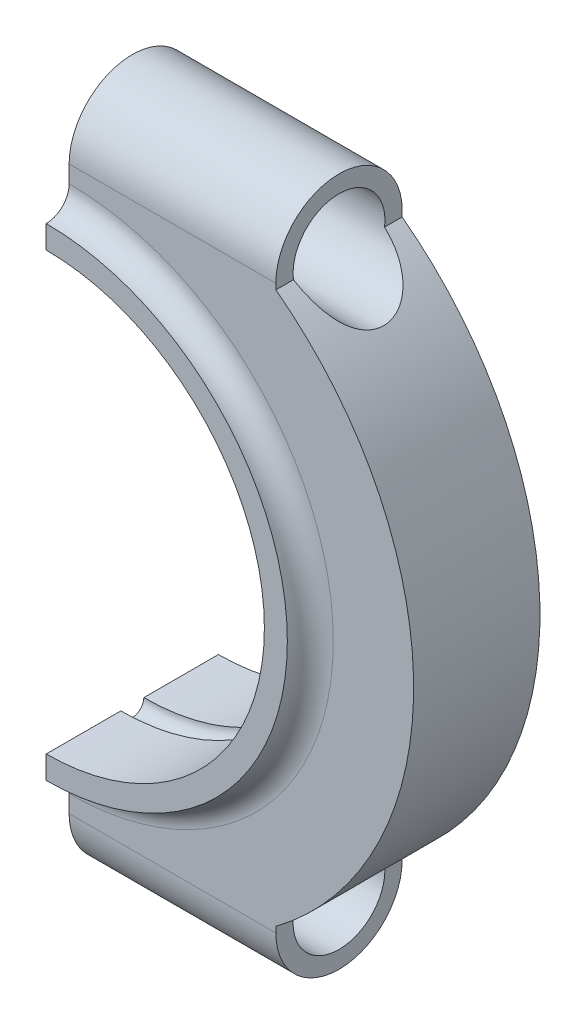
SolidWorks part; units mm, degrees
ref_plane "Front Plane" through (0, 0, 0) normal (0, 0, 1) x (1, 0, 0)
ref_plane "Top Plane" through (0, 0, 0) normal (0, 1, 0) x (1, 0, 0)
ref_plane "Right Plane" through (0, 0, 0) normal (1, 0, 0) x (0, 0, -1)
sketch "Sketch1" plane through (0, 0, 0) normal (0, 0, 1) x (1, 0, 0)
  line L0 (3937, 0) -> (0, 0) construction
  line L1 (-0.057, 762) -> (457.905, 762)
  line L2 (757.2512, 439.1989) -> (773.4704, 438.2517)
  line L3 (1676.1325, 385.5364) -> (3300.7334, 290.6599)
  line L4 (1676.1325, -385.5364) -> (3300.7334, -290.6599)
  line L5 (-0.057, -762) -> (457.905, -762)
  line L6 (-0.057, 762) -> (0, 482.6)
  line L7 (-0.057, -762) -> (0, -482.6)
  arc A0 (0, -482.6) -> (0, 482.6) centre (0, 0) ccw
  circle A1 centre (3937, 0) radius 254
  arc A2 (3718.9531, -387.3446) -> (3718.9531, 387.3446) centre (3937, 0) ccw
  arc A3 (457.905, 762) -> (457.905, -762) centre (0, 0) ccw construction
  arc A4 (3300.7334, 290.6599) -> (3718.9531, 387.3446) centre (3345.1584, 1051.3638) ccw
  arc A5 (457.905, 762) -> (1676.1325, 385.5364) centre (1831.62, 3048) ccw
  arc A6 (3300.7334, -290.6599) -> (3718.9531, -387.3446) centre (3345.1584, -1051.3638) cw
  arc A7 (457.905, -762) -> (1676.1325, -385.5364) centre (1831.62, -3048) cw
  dimension "D1" = 965.2
  dimension "D2" = 508
  dimension "D3" = 889
  dimension "D6" = 1778
  dimension "D9" = 762
  dimension "D10" = 2667
  dimension "D4" = 762
  dimension "D5" = 457.962
  dimension "D7" = 0
  dimension "D8" = 3937
extrude "Boss-Extrude1" add sketch "Sketch1" along normal mid plane 279.4 contours L5 A7 L4 A6 A2 A4 L3 A5 L1 L6 A0 L7 A1 region at (1893.6436, 0, 0)
sketch "Sketch3" plane through (0, 0, 139.7) normal (0, 0, 1) x (1, 0, 0)
  line L0 (3535.7201, -191.1929) -> (817.2234, -349.9527)
  line L1 (1676.1325, -385.5364) -> (3300.7334, -290.6599) construction
  line L2 (3937, 0) -> (0, 0) construction
  line L3 (3535.7201, 191.1929) -> (817.2234, 349.9527)
  arc A1 (3535.7201, 191.1929) -> (3535.7201, -191.1929) centre (3937, 0) ccw
  arc A2 (817.2234, -349.9527) -> (817.2234, 349.9527) centre (0, 0) ccw
  dimension "D1" = 1778
  dimension "D2" = 889
  dimension "D3" = 85.598
extrude "Cut-Extrude1" cut sketch "Sketch3" against normal blind 50.8 and the other way through all
sketch "Sketch4" plane through (0.0984, 0, 0) normal (-1, 0.0002, 0) x (0, 0, 1)
  line L0 (-139.7, 482.6) -> (139.7, 762) construction
  line L1 (-139.7, 762) -> (139.7, 482.6) construction
  line L2 (0, 0) -> (-973.0459, 0) construction
  circle A0 centre (0, 622.3) radius 63.5
  circle A1 centre (0, -622.3) radius 63.5
  dimension "D1" = 127
extrude "Cut-Extrude2" cut sketch "Sketch4" against normal through all both and the other way through all
sketch "Sketch5" plane through (0.0984, 0, 0) normal (-1, -0.0002, 0) x (0, 0, 1)
  circle A0 centre (0, 622.3) radius 101.6
  circle A1 centre (0, -622.3) radius 101.6
  dimension "D1" = 203.2
  dimension "D2" = 203.2
extrude "Cut-Extrude3" cut sketch "Sketch5" against normal through all from offset 508
sketch "Sketch6" plane through (0, 0, 139.7) normal (0, 0, 1) x (1, 0, 0)
  line L0 (-0.057, 762) -> (0, 482.6) construction
  line L1 (-0.057, -762) -> (0, -482.6) construction
  line L2 (-0.0104, 533.4) -> (0, 482.6)
  line L3 (0, -482.6) -> (-0.0104, -533.4)
  arc A0 (0, -482.6) -> (0, 482.6) centre (0, 0) ccw construction
  arc A1 (0, -482.6) -> (0, 482.6) centre (0, 0) ccw
  arc A2 (-0.0104, 533.4) -> (-0.0104, -533.4) centre (0, 0) cw
  dimension "D1" = 533.4
extrude "Boss-Extrude2" add sketch "Sketch6" along normal blind 50.8
mirror "Mirror1" about plane through (0, 0, 0) normal (0, 0, 1) of "Cut-Extrude1", "Boss-Extrude2"
fillet "Fillet1" radius 50.8 2 edges at (533.4, 0, -139.7) (533.4, 0, 139.7)
sketch "Sketch8" plane through (0.0984, 0, 0) normal (-1, -0.0002, 0) x (0, 0, 1)
  line L0 (190.5, 482.6) -> (-190.5, 482.6) construction
  line L1 (0, 0) -> (764.7578, 0) construction
  circle A0 centre (0, 482.6) radius 25.4
  dimension "D1" = 50.8
revolve "Cut-Revolve1" cut sketch "Sketch8" angle 360 about L1
fillet "Fillet3" radius 25.4 8 edges at (3492.5, 0, 88.9) (2176.4718, 270.5728, 88.9) (2176.4718, -270.5728, 88.9) (889, 0, 88.9) (2176.4718, -270.5728, -88.9) (889, 0, -88.9) (3492.5, 0, -88.9) (2176.4718, 270.5728, -88.9)
fillet "Fillet4" 2 edges at (228.924, 762, 139.7) (228.924, 762, -139.7) type full round first side face at (1626.8583, 0, 139.7) second side face at (2176.4718, 0, -139.7) middle face at (228.924, 762, 0)
fillet "Fillet5" 2 edges at (228.924, -762, 139.7) (228.924, -762, -139.7) type full round first side face at (1649.9448, -20.8142, 139.7) second side face at (2176.4718, 0, -139.7) middle face at (228.924, -762, 0)
sketch "Sketch11" plane through (0, 0, 139.7) normal (0, 0, 1) x (1, 0, 0)
  line L0 (457.2, 609.6) -> (457.2, 961.0043)
  line L1 (457.2, 961.0043) -> (5230.0712, 961.0043)
  line L2 (5230.0712, 961.0043) -> (5230.0712, -1342.2405)
  line L3 (5230.0712, -1342.2405) -> (457.143, -1342.2405)
  line L4 (457.143, -1342.2405) -> (457.143, -609.6427)
  arc A0 (457.143, -609.6427) -> (457.2, 609.6) centre (0, 0) ccw
  dimension "D1" = 1524
  dimension "D2" = 457.2
  dimension "D3" = 457.2
extrude "Cut-Extrude4" cut sketch "Sketch11" against normal through all both and the other way through all
